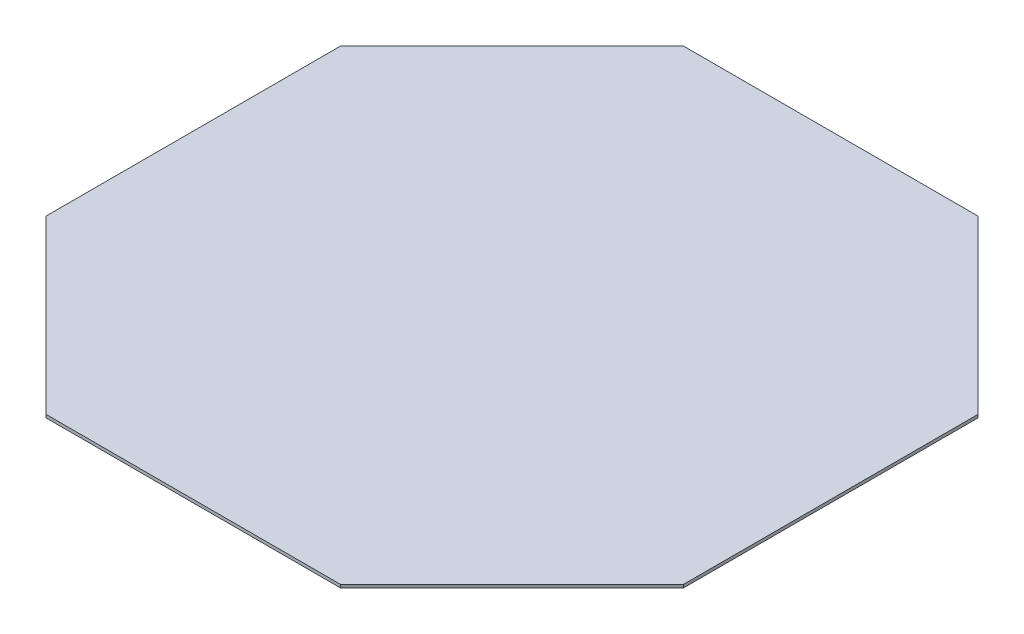
SolidWorks part; units mm, degrees
ref_plane "Front Plane" through (0, 0, 0) normal (0, 0, 1) x (1, 0, 0)
ref_plane "Top Plane" through (0, 0, 0) normal (0, 1, 0) x (1, 0, 0)
ref_plane "Right Plane" through (0, 0, 0) normal (1, 0, 0) x (0, 0, -1)
sketch "Sketch1" plane through (0, 0, 0) normal (0, 1, 0) x (1, 0, 0)
  line L0 (0, 482.6) -> (177.8, 660.4)
  line L1 (0, 0) -> (660.4, 0)
  line L2 (0, 0) -> (0, 660.4)
  line L3 (0, 660.4) -> (660.4, 660.4)
  line L4 (660.4, 0) -> (660.4, 660.4)
  line L5 (330.2, 660.4) -> (330.2, 0) construction
  line L6 (660.4, 482.6) -> (482.6, 660.4)
  line L7 (660.4, 330.2) -> (0, 330.2) construction
  line L8 (660.4, 177.8) -> (482.6, 0)
  line L9 (0, 177.8) -> (177.8, 0)
  point P19 (-267.2391, 926.5385)
  dimension "D1" = 660.4
  dimension "D2" = 660.4
  dimension "D3" = 177.8
  dimension "D4" = 177.8
extrude "Boss-Extrude1" add sketch "Sketch1" along normal blind 3.175 contours L2 L9 L1 L8 L4 L6 L3 L0 region at (330.2, 0, -330.2)
